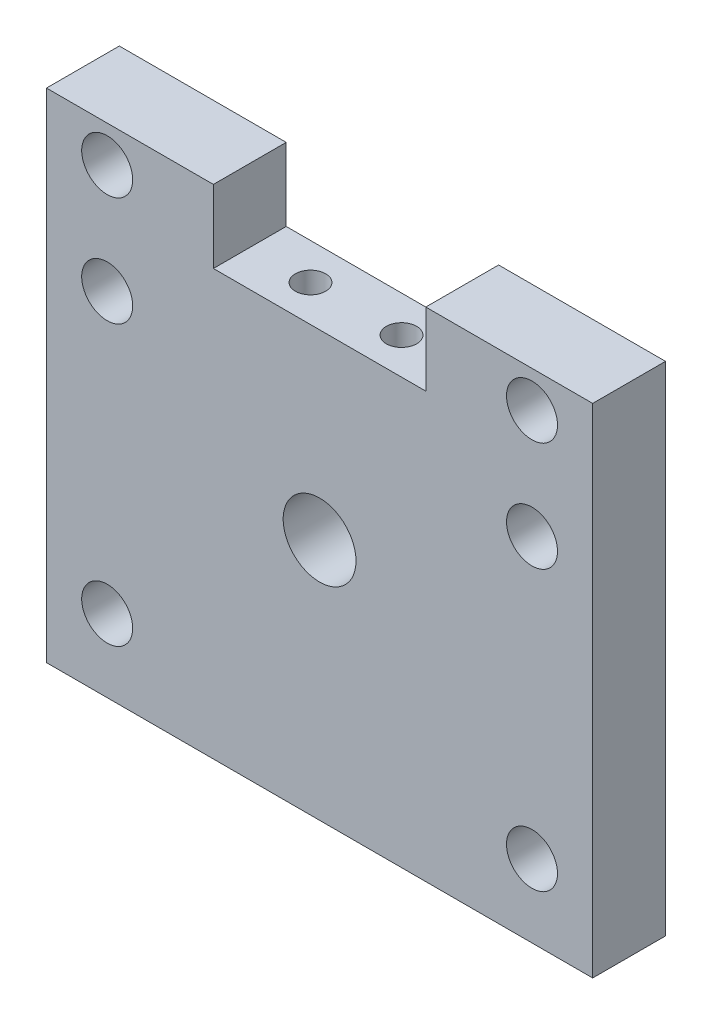
SolidWorks part; units mm, degrees
material "K110"
ref_plane "Front Plane" through (0, 0, 0) normal (0, 0, 1) x (1, 0, 0)
ref_plane "Top Plane" through (0, 0, 0) normal (0, 1, 0) x (1, 0, 0)
ref_plane "Right Plane" through (0, 0, 0) normal (1, 0, 0) x (0, 0, -1)
sketch "Sketch1" plane through (0, 0, 0) normal (0, 0, 1) x (1, 0, 0)
  line L1 (-45, -41) -> (45, -41)
  line L2 (-45, -41) -> (-45, 41)
  line L3 (-45, 41) -> (45, 41)
  line L4 (45, -41) -> (45, 41)
  line L5 (-45, -41) -> (45, 41) construction
  line L6 (-45, 41) -> (45, -41) construction
  point P0 (0, 0)
  dimension "D1" = 90
  dimension "D2" = 82
extrude "Boss-Extrude1" add sketch "Sketch1" along normal mid plane 12 contours L3 L4 L1 L2
hole_wizard "M8 Clearance Hole1" positions "Sketch5" profile "Sketch3" hole size "M8" standard "ISO" end condition through all
sketch "Sketch5" plane through (0, 0, 6) normal (0, 0, 1) x (1, 0, 0)
  point P0 (-35, 17)
  point P3 (35, 17)
  point P6 (35, -29)
  point P9 (-35, -29)
  point P13 (-35, 35)
  point P16 (35, 35)
sketch "Sketch3" plane through (-35, 17, 6) normal (1, 0, 0) x (0, -1, 0)
  line L0 (0, 0) -> (0, 12)
  line L1 (0, 12) -> (4.2, 12)
  line L2 (4.2, 12) -> (4.2, 0)
  line L5 (4.2, 0) -> (0, 0)
  line L11 (0, -6.35) -> (0, 107.95) construction
  dimension "Thru Hole Dia." = 8.4
  dimension "Thru Hole Depth" = 12
sketch "Sketch6" plane through (0, 41, 0) normal (0, 1, 0) x (1, 0, 0)
  line L0 (-45, -6) -> (45, -6) construction
  line L1 (17.5, -6) -> (-17.5, -6)
  line L2 (17.5, -6) -> (17.5, 6)
  line L3 (17.5, 6) -> (-17.5, 6)
  line L4 (-17.5, -6) -> (-17.5, 6)
  line L5 (-45, 6) -> (45, 6) construction
  line L6 (0, -6) -> (0, 6) construction
  dimension "D1" = 35
extrude "Cut-Extrude1" cut sketch "Sketch6" against normal blind 12 and the other way through all
hole_wizard "Ø12.0 (12) Diameter Hole1" positions "Sketch9" profile "Sketch8" hole size "Ø12.0" standard "ISO" end condition through all
sketch "Sketch9" plane through (0, 0, 6) normal (0, 0, 1) x (1, 0, 0)
  point P2 (0, -1)
sketch "Sketch8" plane through (0, -1, 6) normal (1, 0, 0) x (0, -1, 0)
  line L0 (0, 0) -> (0, 12)
  line L1 (0, 12) -> (6, 12)
  line L2 (6, 12) -> (6, 0)
  line L5 (6, 0) -> (0, 0)
  line L11 (0, -6.35) -> (0, 107.95) construction
  dimension "Thru Hole Dia." = 12
  dimension "Thru Hole Depth" = 12
hole_wizard "M6 Tapped Hole1" positions "Sketch12" profile "Sketch11" tap size "M6" standard "ISO"
sketch "Sketch12" plane through (0, 29, 0) normal (0, 1, 0) x (1, 0, 0)
  point P0 (-7.5, 0)
  point P3 (7.5, 0)
sketch "Sketch11" plane through (-7.5, 29, 0) normal (1, 0, 0) x (0, 0, 1)
  line L0 (0, 0) -> (0, 17)
  line L1 (0, 17) -> (2.5, 15.4978)
  line L2 (2.5, 15.4978) -> (2.5, 0)
  line L5 (2.5, 0) -> (0, 0)
  line L10 (0, 17) -> (-2.5, 15.4978) construction
  line L11 (0, -6.35) -> (0, 107.95) construction
  dimension "Tap Drill Dia." = 5
  dimension "Tap Drill Depth" = 17
  dimension "Drill Angle" = 118
cosmetic thread "Hole Thread1"
cosmetic thread "Hole Thread2"
